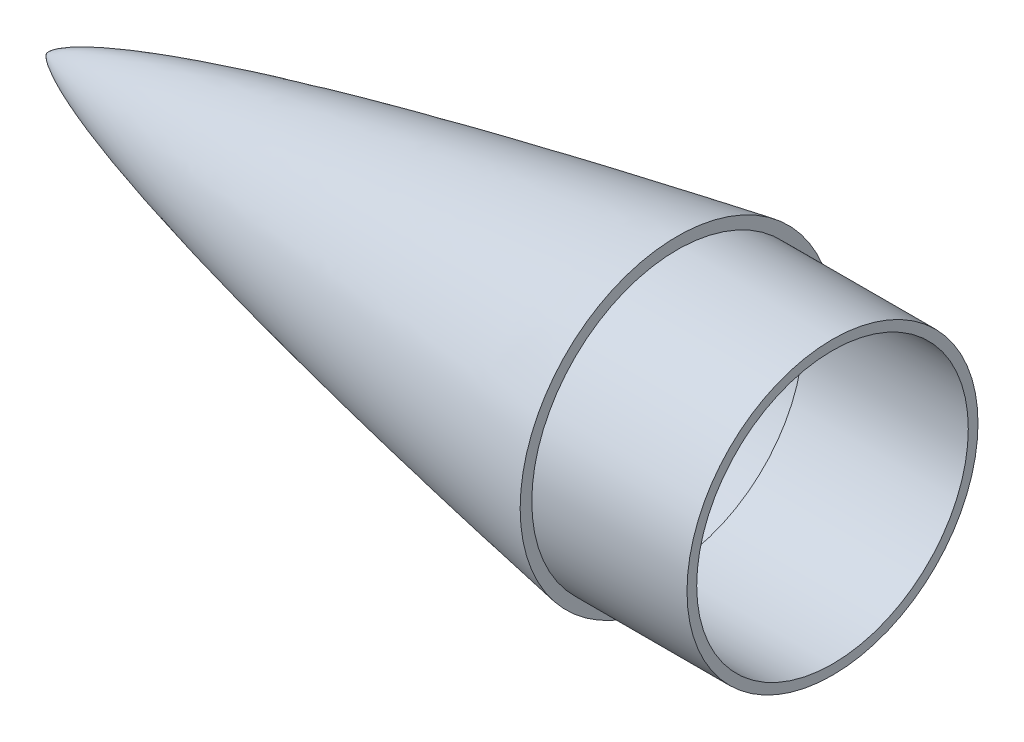
SolidWorks part; units mm, degrees
ref_plane "Front Plane" through (0, 0, 0) normal (0, 0, 1) x (1, 0, 0)
ref_plane "Top Plane" through (0, 0, 0) normal (0, 1, 0) x (1, 0, 0)
ref_plane "Right Plane" through (0, 0, 0) normal (1, 0, 0) x (0, 0, -1)
sketch "Sketch2" plane through (0, 0, 0) normal (0, 1, 0) x (1, 0, 0)
  line L2 (0, 0) -> (165.1, 0)
  line L3 (165.1, 0) -> (165.1, 41.148)
  spline S0 degree 4 poles (0, 0) (0.0013, 0.0109) (0.0052, 0.0324) (0.0185, 0.0743) (0.0479, 0.1412) (0.0923, 0.2209) (0.1619, 0.3258) (0.2647, 0.459) (0.419, 0.633) (0.6657, 0.8752) (1.0601, 1.2125) (1.71, 1.6954) (2.8003, 2.3961) (4.6639, 3.4266) (7.8144, 4.9187) (13.3082, 7.1445) (21.4411, 9.949) (31.8592, 13.0859) (43.9844, 16.3588) (56.6175, 19.4952) (69.2965, 22.4416) (82.0083, 25.2395) (93.1547, 27.582) (102.7204, 29.5265) (110.7015, 31.1097) (117.0863, 32.3547) (122.6847, 33.4284) (127.471, 34.3349) (131.4847, 35.0872) (134.6535, 35.6773) (137.9101, 36.2785) (141.0137, 36.8489) (144.3738, 37.4601) (147.33, 37.997) (151.7413, 38.7883) (155.8164, 39.5179) (163.2409, 40.8257) (167.7218, 41.6061) (174.4586, 42.7703) (177.6383, 43.3104) (180.3185, 43.769) (180.9327, 43.8713) (181.6516, 43.9942) knots 0 0 0 0 0 0.000233 0.000466 0.000933 0.001555 0.002176 0.003146 0.004516 0.006507 0.009537 0.014197 0.021756 0.034103 0.054886 0.088436 0.148008 0.217349 0.28669 0.35603 0.425371 0.494712 0.564052 0.598723 0.633393 0.668064 0.702734 0.720069 0.737404 0.754739 0.772075 0.78941 0.806745 0.82408 0.841415 0.876086 0.910756 0.955378 0.977689 0.988845 1 1 1 1 1 construction
  spline S1 degree 4 poles (0, 0) (0.0013, 0.0109) (0.0052, 0.0324) (0.0185, 0.0743) (0.0479, 0.1412) (0.0923, 0.2209) (0.1619, 0.3258) (0.2647, 0.459) (0.419, 0.633) (0.6657, 0.8752) (1.0601, 1.2125) (1.71, 1.6954) (2.8003, 2.3961) (4.6639, 3.4266) (7.8144, 4.9187) (13.3082, 7.1445) (21.4411, 9.949) (31.8592, 13.0859) (43.9844, 16.3588) (56.6175, 19.4952) (69.2965, 22.4416) (82.0083, 25.2395) (93.1547, 27.582) (102.7204, 29.5265) (110.7015, 31.1097) (117.0863, 32.3547) (122.6847, 33.4284) (127.471, 34.3349) (131.4847, 35.0872) (134.6535, 35.6773) (137.9101, 36.2785) (141.0137, 36.8489) (144.3738, 37.4601) (147.33, 37.997) (151.7413, 38.7883) (155.8164, 39.5179) (160.7177, 40.3813) (163.6402, 40.8933) (165.1, 41.148) knots 0 0 0 0 0 0.000233 0.000466 0.000933 0.001555 0.002176 0.003146 0.004516 0.006507 0.009537 0.014197 0.021756 0.034103 0.054886 0.088436 0.148008 0.217349 0.28669 0.35603 0.425371 0.494712 0.564052 0.598723 0.633393 0.668064 0.702734 0.720069 0.737404 0.754739 0.772075 0.78941 0.806745 0.82408 0.841415 0.876086 0.910756 0.910756 0.910756 0.910756 0.910756
revolve "Revolve1" add sketch "Sketch2" angle 360 about L2
sketch "Sketch8" plane through (165.1, 0, 0) normal (1, 0, 0) x (0, 0, -1)
  circle A0 centre (0, 0) radius 38.1
  dimension "D1" = 76.2
extrude "Boss-Extrude2" add sketch "Sketch8" along normal blind 40.64
shell "Shell2" thickness 2.54 removed face at (205.74, 0, -38.1)
